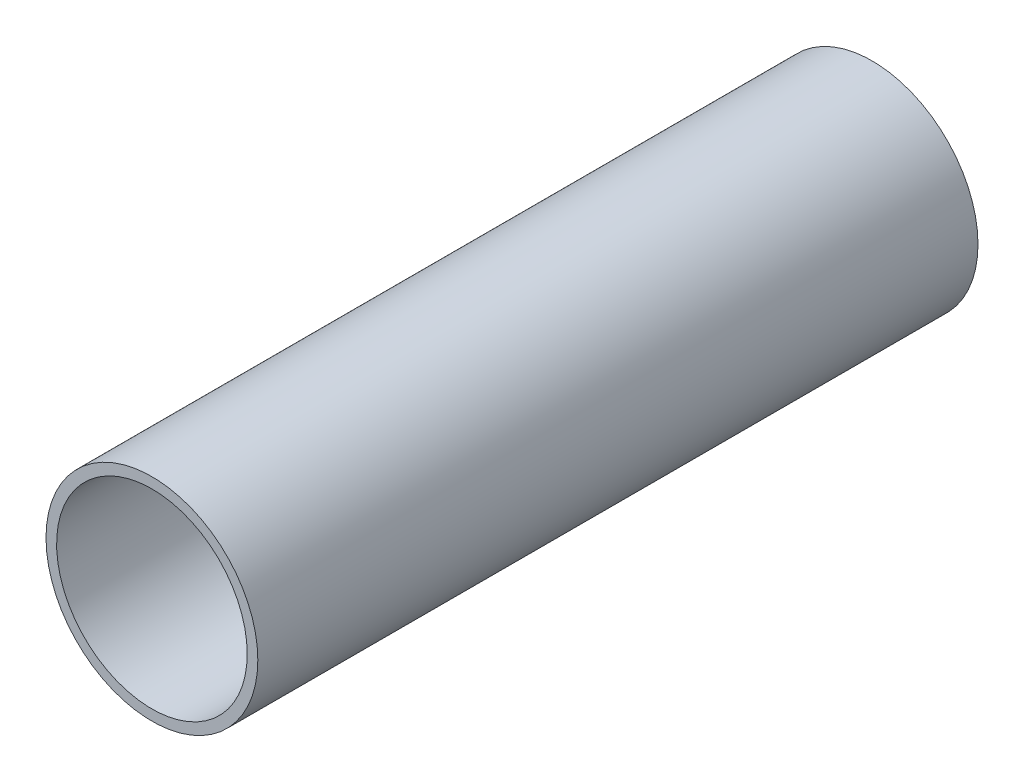
SolidWorks part; units mm, degrees
ref_plane "Front Plane" through (0, 0, 0) normal (0, 0, 1) x (1, 0, 0)
ref_plane "Top Plane" through (0, 0, 0) normal (0, 1, 0) x (1, 0, 0)
ref_plane "Right Plane" through (0, 0, 0) normal (1, 0, 0) x (0, 0, -1)
sketch "Sketch2" plane through (0, 0, 0) normal (0, 0, 1) x (1, 0, 0)
  line L0 (0, 0) -> (0, 7.5) construction
  line L1 (0, 0) -> (0, -7.5) construction
  line L2 (-6.75, 0) -> (6.75, 0) construction
  circle A0 centre (0, 0) radius 7.5
  circle A1 centre (0, 0) radius 6.75
  dimension "D1" = 15
  dimension "D2" = 13.5
extrude "Boss-Extrude2" add sketch "Sketch2" along normal blind 50
sketch "Sketch5" plane through (0, 0, 0) normal (0, 0, -1) x (-1, 0, 0)
  line L0 (6.75, 0) -> (-6.75, 0) construction
  line L1 (0, 6.75) -> (0, -6.75) construction
  circle A0 centre (0, 0) radius 6.75 construction
  circle A1 centre (0, 0) radius 7.5
  circle A2 centre (0, 6.75) radius 1
  circle A3 centre (0, -6.75) radius 1
  circle M3 centre (0, 0) radius 7.5
  circle M4 centre (0, 0) radius 6.75
  dimension "D1" = 15
  dimension "D2" = 2
extrude "Boss-Extrude4" add sketch "Sketch5" along normal blind 1 contours A2 M4 | A2 M4 | A3 A1 A2 M4 | A3 A2 M3 M4 | A3 M4 | A3 M4 region at (-5.4228, -4.9405, 0) region at (0, 7.0851, 0) region at (0, -7.0851, 0) region at (1.0882, 7.1635, 0) region at (0, 6.3125, 0) region at (0, -6.3125, 0)
